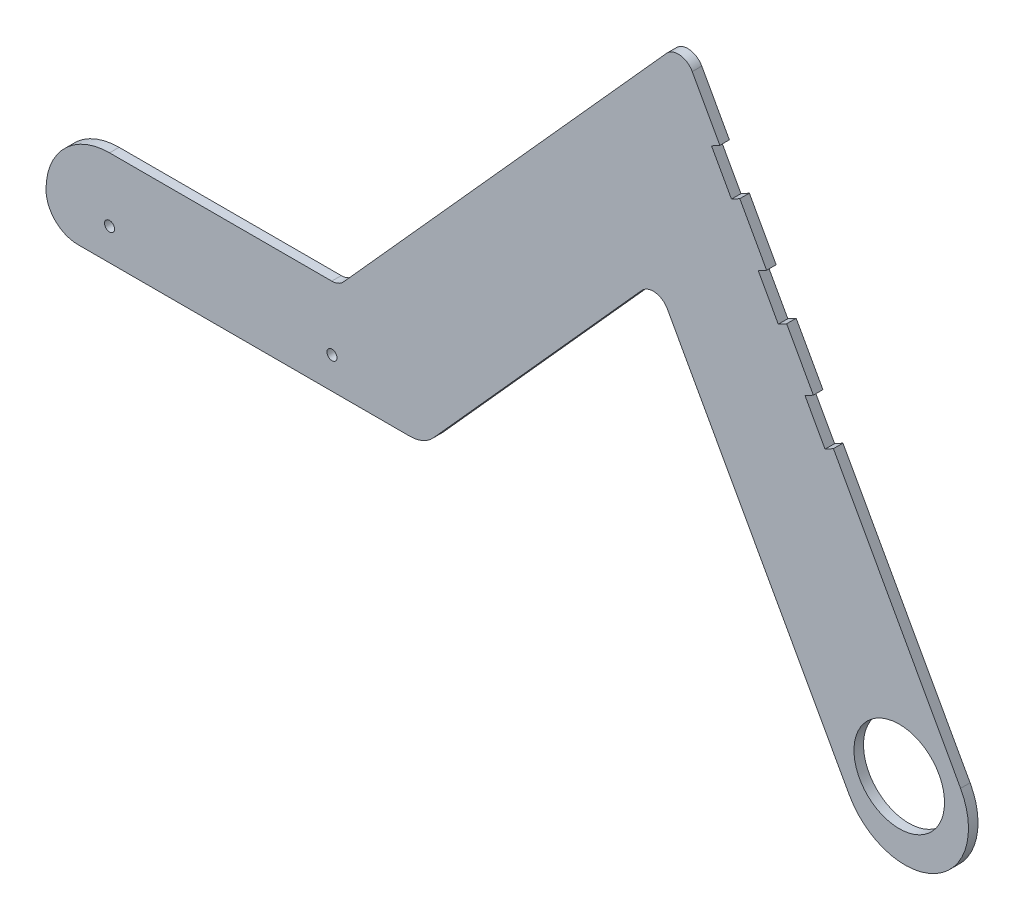
SolidWorks part; units mm, degrees
ref_plane "Front Plane" through (0, 0, 0) normal (0, 0, 1) x (1, 0, 0)
ref_plane "Top Plane" through (0, 0, 0) normal (0, 1, 0) x (1, 0, 0)
ref_plane "Right Plane" through (0, 0, 0) normal (1, 0, 0) x (0, 0, -1)
sketch "Croquis1" plane through (0, 0, 0) normal (0, 0, 1) x (1, 0, 0)
  line L0 (-135.8112, 31.6609) -> (-65.8732, 31.6609)
  line L1 (-62.1542, 33.3189) -> (39.488, 146.4297)
  line L2 (47.5853, 145.5024) -> (132.0431, -7.6343)
  line L3 (97.017, -26.9519) -> (39.7313, 76.9171)
  line L4 (31.634, 77.8443) -> (-44.3213, -6.6811)
  line L5 (-48.0403, -8.3391) -> (-135.8112, -8.3391)
  arc A0 (132.0431, -7.6343) -> (97.017, -26.9519) centre (114.53, -17.2931) cw
  arc A1 (-135.8112, -8.3391) -> (-135.8112, 31.6609) centre (-135.8112, 11.6609) cw
  circle A3 centre (-135.8112, 11.6609) radius 1.58
  circle A4 centre (-65.8112, 11.5885) radius 1.58
  circle A6 centre (112.7386, -14.0449) radius 14.25
  arc A7 (-62.1542, 33.3189) -> (-65.8732, 31.6609) centre (-65.8732, 36.6609) cw
  arc A8 (47.5853, 145.5024) -> (39.488, 146.4297) centre (43.2071, 143.0877) ccw
  arc A9 (39.7313, 76.9171) -> (31.634, 77.8443) centre (35.353, 74.5024) ccw
  arc A10 (-44.3213, -6.6811) -> (-48.0403, -8.3391) centre (-48.0403, -3.3391) cw
  point P17 (-155.8112, 11.6609)
  point P18 (124.1888, -34.8061)
  point P22 (44.1888, 151.6609)
  point P27 (-45.8112, -8.3391)
  dimension "D10" = 3.16
  dimension "D11" = 28.5
  dimension "D13" = 5
  dimension "D1" = 40
  dimension "D2" = 40
  dimension "D3" = 40
  dimension "D4" = 70
  dimension "D5" = 90
  dimension "D6" = 280
  dimension "D7" = 46.467
  dimension "D8" = 90
  dimension "D9" = 120
  dimension "D12" = 20
extrude "Saliente-Extruir1" add sketch "Croquis1" along normal blind 3
sketch "Croquis3" plane through (98.0182, 54.0589, 0) normal (0.8757, 0.4829, 0) x (0, 0, -1)
  line L0 (-3, -70.4538) -> (-3, 104.4289) construction
  line L1 (-3, 86.4289) -> (0, 86.4289)
  line L2 (-3, 86.4289) -> (-3, 73.4264)
  line L3 (-3, 73.4264) -> (0, 73.4264)
  line L4 (0, 86.4289) -> (0, 73.4264)
  line L5 (0, 86.4289) -> (-3, 86.4289) construction
  line L6 (0, -70.4538) -> (0, 104.4289) construction
  line L7 (0, 55.953) -> (-3, 55.953) construction
  line L8 (-3, 55.953) -> (0, 55.953)
  line L9 (-3, 55.953) -> (-3, 42.9048)
  line L10 (-3, 42.9048) -> (0, 42.9048)
  line L11 (0, 55.953) -> (0, 42.9048)
  line L12 (0, 42.9048) -> (-3, 42.9048) construction
  line L13 (0, 25.4771) -> (-3, 25.4771) construction
  line L14 (-3, 25.4771) -> (0, 25.4771)
  line L15 (-3, 25.4771) -> (-3, 12.4289)
  line L16 (-3, 12.4289) -> (0, 12.4289)
  line L17 (0, 25.4771) -> (0, 12.4289)
  line L18 (0, 12.4289) -> (-3, 12.4289) construction
extrude "Cortar-Extruir1" cut sketch "Croquis3" against normal blind 3
sketch "Croquis4" plane through (0, 0, 3) normal (0, 0, 1) x (1, 0, 0)
  line L1 (-177.2002, -8.3391) -> (-13.5247, -8.3391)
  line L2 (-177.2002, -8.3391) -> (-177.2002, 1.6609)
  line L3 (-177.2002, 1.6609) -> (-13.5247, 1.6609)
  line L4 (-13.5247, -8.3391) -> (-13.5247, 1.6609)
  dimension "D1" = 10
extrude "Cortar-Extruir2" cut sketch "Croquis4" against normal blind 10
fillet "Redondeo1" radius 10 2 edges at (-36.8251, 1.6609, 1.5) (-153.1317, 1.6609, 1.5)
sketch "Croquis5" plane through (0, 0, 3) normal (0, 0, 1) x (1, 0, 0)
  line L0 (-135.8112, 11.6609) -> (-65.8112, 11.5885) construction
  line L1 (112.7386, -14.0449) -> (112.7386, 11.5885) construction
  line L2 (112.7386, 11.5885) -> (-65.8112, 11.5885) construction
  line L3 (43.7759, 148.0552) -> (43.7759, 11.5885) construction
  line L4 (35.9219, 79.4699) -> (35.9219, 11.5885) construction
  line L5 (56.2782, 129.7406) -> (24.4911, 129.7406) construction
  line L6 (39.488, 146.4297) -> (-62.1542, 33.3189) construction
  line L7 (-33.8452, 4.9769) -> (31.634, 77.8443) construction
  line L8 (39.7313, 76.9171) -> (97.017, -26.9519) construction
  circle A0 centre (-135.8112, 11.6609) radius 1.58
  circle A1 centre (112.7386, -14.0449) radius 14.25
  arc A2 (47.5853, 145.5024) -> (39.488, 146.4297) centre (43.2071, 143.0877) ccw construction
  arc A3 (39.7313, 76.9171) -> (31.634, 77.8443) centre (35.353, 74.5024) ccw construction
  arc A4 (97.017, -26.9519) -> (132.0431, -7.6343) centre (114.53, -17.2931) ccw construction
  point P25 (-27.904, 11.5885)
  point P26 (75.7612, 11.5885)
  point P29 (112.7386, -37.2127)
  point P32 (134.2645, -14.0449)
  point P36 (89.8985, -14.0449)
  point P37 (97.017, -26.9519)
  dimension "D1" = 3.16
  dimension "D2" = 28.5
  dimension "D3" = 21.5259
  dimension "D4" = 22.8401
  dimension "D5" = 23.1678
